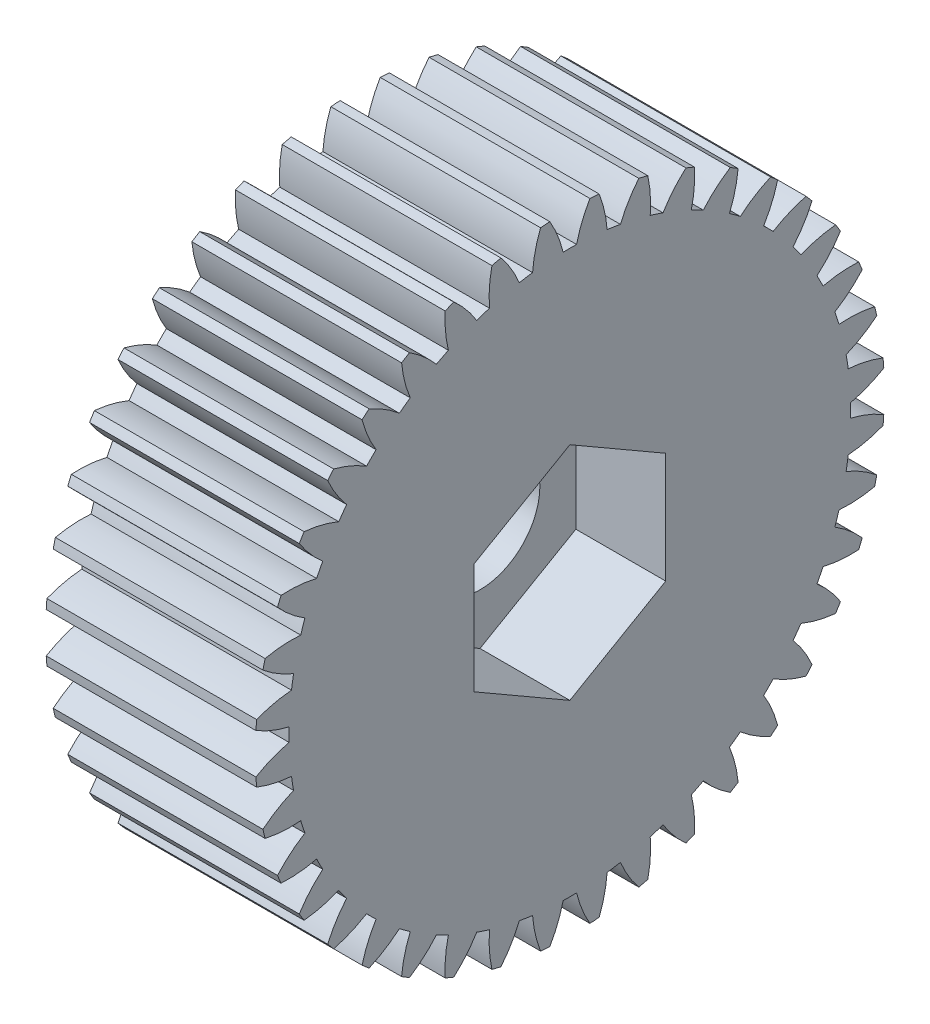
SolidWorks part; units mm, degrees
ref_plane "Plane1" through (0, 0, 0) normal (0, 0, 1) x (1, 0, 0)
ref_plane "Plane2" through (0, 0, 0) normal (0, 1, 0) x (1, 0, 0)
ref_plane "Plane3" through (0, 0, 0) normal (1, 0, 0) x (0, 0, -1)
sketch "HoldingSke" plane through (0, 0, 0) normal (0, 1, 0) x (1, 0, 0)
  line L0 (0, 0) -> (0.766, -0.6428)
  line L1 (-15, 0) -> (100, 0) construction
  line L2 (0, 0) -> (-2.1039, 2.3779)
  line L3 (0, 0) -> (-11.863, 4.5341)
  line L4 (0, 0) -> (6.6156, 5.5511)
  line L5 (0, 0) -> (-46.8476, -17.4728)
  line L6 (0, 0) -> (-11.6055, -7.8303)
  line L7 (-2.1039, 2.3779) -> (8.6586, 51.2059)
  line L8 (-76.2, 54.61) -> (-75.5, 54.61)
  line L9 (-71.009, 38.7566) -> (-53.1078, 45.2721)
  line L10 (-76.2, 71.12) -> (104.1128, 71.12)
  line L11 (0, 0) -> (-14, 0)
  line L12 (-76.2, 101.6) -> (-76.162, 101.6)
  line L13 (24.9733, 27.94) -> (52.9518, 28.4284)
  line L14 (24.9733, 27.94) -> (24.9743, 27.94)
  line L15 (24.9733, 27.94) -> (100.4006, 29.5858)
  line L16 (-63.627, -1) -> (-12.827, -1)
  circle A0 centre (0, 0) radius 2
  circle A1 centre (0, 0) radius 18.749
  circle A2 centre (0, 0) radius 37.5
  circle A3 centre (0, 0) radius 2
  dimension "MHD" = 37.498
  dimension "Hub_dia" = 75
  dimension "Bore" = 4
  dimension "MBD" = 4
  dimension "Num_teeth" = 40
  dimension "Pitch" = 1
  dimension "Overall_len" = 50
  dimension "Show_teeth" = 40
  dimension "Thickness" = 14
  dimension "OAL" = 50.0001
  dimension "T_dim" = 0.7
  dimension "Ap" = 20
  dimension "H" = 19.05
  dimension "Pitch_radius" = 180.3128
  dimension "Width" = 14
  dimension "Backlash" = 0.038
  dimension "Addendum_fac" = 1
  dimension "Dedendum_fac" = 1.25
  dimension "Clearance_fac" = 0.25
  dimension "Dedendum_add" = 0.001
  dimension "Module" = 1
sketch "BasProSke" plane through (0, 0, 0) normal (0, 1, 0) x (1, 0, 0)
  line L0 (-10, 0) -> (60, 0) construction
  line L1 (0, 0) -> (0, 21)
  line L2 (0, 0) -> (14, 0)
  line L3 (14, 0) -> (14, 21)
  line L4 (14, 21) -> (0, 21)
  dimension "Thickness" = 14
  dimension "Diameter" = 42
revolve "Base-Revolve" add sketch "BasProSke" angle 360 about L0
sketch "TooCutSke" plane through (0, 0, 0) normal (1, 0, 0) x (0, 0, -1)
  line L1 (0, 0) -> (0, 107) construction
  line L2 (0, 0) -> (-0.8517, 19.9819) construction
  line L3 (0, 0) -> (-3.1363, 39.8509) construction
  line L4 (-0.8517, 19.9819) -> (-1.5682, 19.9255) construction
  arc A0 (0.4487, 18.7436) -> (-0.4487, 18.7436) centre (0, 0) ccw
  arc A1 (1.3547, 20.9817) -> (-1.3547, 20.9817) centre (0, 0) ccw
  circle A2 centre (0, 0) radius 20 construction
  circle A3 centre (0, 0) radius 18.7939 construction
  arc A4 (-0.4487, 18.7436) -> (-1.3547, 20.9817) centre (-8.2322, 16.895) ccw
  arc A5 (1.3547, 20.9817) -> (0.4487, 18.7436) centre (8.2322, 16.895) ccw
  dimension "Root_dia" = 37.498
  dimension "Overcut_dia" = 42.0508
  dimension "Pitch_dia" = 40
  dimension "Base_dia" = 37.5877
  dimension "Flank_rad" = 8
  dimension "Half_ang" = 4.5
  dimension "Half_CT" = 0.7187
extrude "ToothCut" cut sketch "TooCutSke" along normal through all
fillet "Breaks" [suppressed] radius 0.02 tangent propagation no
fillet "RootFillets" [suppressed] radius 0.251
pattern_circular "TeethCuts" count 40 every 9 about axis through (-10, 0, 0) along (1, 0, 0) of "ToothCut", "RootFillets", "Breaks"
sketch "HubNeaOneSke" plane through (0, 0, 0) normal (-1, 0, 0) x (0, 0, 1)
  circle A0 centre (0, 0) radius 18.749
  dimension "Diameter" = 37.498
extrude "HubNearOne" [suppressed] add sketch "HubNeaOneSke" along normal blind 36.0001
sketch "HubNeaBotSke" plane through (0, 0, 0) normal (-1, 0, 0) x (0, 0, 1)
  circle A0 centre (0, 0) radius 18.749
  dimension "Diameter" = 37.498
extrude "HubNearBoth" [suppressed] add sketch "HubNeaBotSke" along normal blind 18
ref_plane "FarPln" through (14, 0, 0) normal (1, 0, 0) x (0, 0, -1)
sketch "HubFarSke" plane through (14, 0, 0) normal (1, 0, 0) x (0, 0, -1)
  circle A0 centre (0, 0) radius 18.749
  dimension "Diameter" = 37.498
extrude "HubFar" [suppressed] add sketch "HubFarSke" along normal blind 18
sketch "BorSke" plane through (0, 0, 0) normal (1, 0, 0) x (0, 0, -1)
  circle A0 centre (0, 0) radius 2
extrude "Bore" cut sketch "BorSke" along normal mid plane 100.0001
sketch "KeySke" plane through (0, 0, 0) normal (1, 0, 0) x (0, 0, -1)
  line L0 (-0.8, 0) -> (-0.8, 2.7)
  line L1 (-0.8, 2.7) -> (0.8, 2.7)
  line L2 (0.8, 2.7) -> (0.8, 0)
  line L3 (0, 0) -> (0, 34) construction
  line L4 (-0.8, 0) -> (0.8, 0)
  dimension "Offset" = 2.7
  dimension "Width" = 1.6
extrude "Keyway" [suppressed] cut sketch "KeySke" along normal mid plane 100.0001
pattern_circular "Keyway2" [suppressed] count 2 every 90 about axis through (-10, 0, 0) along (1, 0, 0)
sketch "Sketch1" plane through (14, 0, 0) normal (1, 0, 0) x (0, 0, -1)
  line L1 (0, 7.3901) -> (-6.4, 3.695)
  line L2 (-6.4, 3.695) -> (-6.4, -3.695)
  line L3 (-6.4, -3.695) -> (0, -7.3901)
  line L4 (0, -7.3901) -> (6.4, -3.695)
  line L5 (6.4, -3.695) -> (6.4, 3.695)
  line L6 (6.4, 3.695) -> (0, 7.3901)
  circle A0 centre (0, 0) radius 7.3901
  circle A2 centre (0, 0) radius 6.4 construction
  circle A3 centre (0, 0) radius 4
  dimension "D1" = 8
  dimension "D2" = 12.8
extrude "Cut-Extrude1" cut sketch "Sketch1" against normal blind 6 contours L1 L2 L3 L4 L5 L6
extrude "Cut-Extrude2" cut sketch "Sketch1<7>" against normal through all contours A3 region at (14, 0, 0)
sketch "Sketch1<7>" plane through (14, 0, 0) normal (1, 0, 0) x (0, 0, -1) same geometry as "Sketch1"
sketch "Sketch2" plane through (0, 0, 0) normal (-1, 0, 0) x (0, 0, 1)
  circle A0 centre (0, 0) radius 6.5
  circle A1 centre (0, 0) radius 4
  dimension "D1" = 13
  dimension "D2" = 8
extrude "Boss-Extrude1" add sketch "Sketch2" along normal blind 3.8
sketch "Sketch3" plane through (8, 0, 0) normal (1, 0, 0) x (0, 0, -1)
  line L1 (4, 4) -> (-4, 4)
  line L2 (4, 4) -> (4, -4)
  line L3 (4, -4) -> (-4, -4)
  line L4 (-4, 4) -> (-4, -4)
  line L6 (5.5, 5.5) -> (5.5, -5.5)
  line L7 (5.5, -5.5) -> (-5.5, -5.5)
  line L8 (-5.5, 5.5) -> (-5.5, -5.5)
  line L9 (5.5, 5.5) -> (-5.5, 5.5)
  line L10 (5.5, 4) -> (5.8718, 4)
  line L11 (6.4, 3.695) -> (0, 7.3901) construction
  line L12 (5.5, -4) -> (5.8718, -4)
  line L13 (0, -7.3901) -> (6.4, -3.695) construction
  line L14 (-5.5, -4) -> (-5.8718, -4)
  line L15 (-6.4, -3.695) -> (0, -7.3901) construction
  line L16 (-5.5, 4) -> (-5.8718, 4)
  line L17 (0, 7.3901) -> (-6.4, 3.695) construction
  circle A0 centre (0, 0) radius 4 construction
  line M10 (6.4, 3.695) -> (0, 7.3901)
  line M11 (0, 7.3901) -> (-6.4, 3.695)
  line M13 (-6.4, -3.695) -> (0, -7.3901)
  line M14 (0, -7.3901) -> (6.4, -3.695)
  dimension "D1" = 1.5
extrude "Boss-Extrude2" [suppressed] add sketch "Sketch3" along normal blind 0.3 contours L9 L8 L7 L6 L4 L1 L2 L3 M10 M11 M13 M14 | L12 L6 M14 | L6 L10 M10 | L16 L8 M11 | L8 L14 M13
equation "' \"Module@HoldingSke\" = 6.35"
equation "' \"Num_teeth@HoldingSke\" = 12"
equation "' \"Ap@HoldingSke\" =  20"
equation "' \"Ap@HoldingSke\" = 20"
equation "' \"Width@HoldingSke\" = 0.5 * 25.4"
equation "' \"Hub_dia@HoldingSke\"= 1 * 25.4"
equation "' \"Hub_dia@HoldingSke\" = 1 * 25.4"
equation "' \"Overall_len@HoldingSke\" = 1.0 * 25.4"
equation "' \"Bore@HoldingSke\" = 0.75 * 25.4"
equation "' \"T_dim@HoldingSke\" = 0.1 * 25.4"
equation "' \"Width@KeySke\" = 0.25 * 25.4"
equation "' \"Show_teeth@HoldingSke\" = 13"
equation "' \"Backlash@HoldingSke\" = 0.009 * 25.4"
equation "' \"Addendum_fac@HoldingSke\" = 1.0"
equation "' \"Dedendum_fac@HoldingSke\" = 1.25"
equation "' \"Dedendum_add@HoldingSke\" = 0.00005 * 25.4"
equation "' \"Clearance_fac@HoldingSke\" = 0.25"
equation "\"Pitch@HoldingSke\" = 1 / \"Module@HoldingSke\""
equation "\"Overcut_dia@TooCutSke\" = (\"Num_teeth@HoldingSke\" + 2 * \"Addendum_fac@HoldingSke\") / \"Pitch@HoldingSke\" + 0.002 * 25.4"
equation "\"Pitch_dia@TooCutSke\" = \"Num_teeth@HoldingSke\" / \"Pitch@HoldingSke\""
equation "\"Base_dia@TooCutSke\" = \"Num_teeth@HoldingSke\" / \"Pitch@HoldingSke\" * cos((\"Ap@HoldingSke\"  * 3.14159265 / 180))"
equation "\"Root_dia@TooCutSke\" = (\"Num_teeth@HoldingSke\" + 2) / \"Pitch@HoldingSke\" - 2 * (\"Addendum_fac@HoldingSke\" + \"Dedendum_fac@HoldingSke\") / \"Pitch@HoldingSke\" - \"Dedendum_add@HoldingSke\" * 2"
equation "\"Half_ang@TooCutSke\" = 180 / \"Num_teeth@HoldingSke\""
equation "\"Half_CT@TooCutSke\" = \"Num_teeth@HoldingSke\" / \"Pitch@HoldingSke\" * sin((3.14159265 / 2 / \"Num_teeth@HoldingSke\")) / 2 - 7 * \"Backlash@HoldingSke\" / 4"
equation "\"Flank_rad@TooCutSke\" = \"Num_teeth@HoldingSke\" / \"Pitch@HoldingSke\" / 5"
equation "\"Radius@RootFillets\" = \"Clearance_fac@HoldingSke\" / \"Pitch@HoldingSke\" + \"Dedendum_add@HoldingSke\""
equation "\"Break_rad@Breaks\" = 0.02 / \"Pitch@HoldingSke\""
equation "\"Thickness@HoldingSke\" = \"Width@HoldingSke\""
equation "\"OAL@HoldingSke\" = \"Thickness@HoldingSke\""
equation "\"MHD@HoldingSke\" = (\"Num_teeth@HoldingSke\" + 2) / \"Pitch@HoldingSke\" - 2 * (\"Addendum_fac@HoldingSke\" + \"Dedendum_fac@HoldingSke\")  / \"Pitch@HoldingSke\" - \"Dedendum_add@HoldingSke\" * 2"
equation "\"MBD@HoldingSke\" = (\"Num_teeth@HoldingSke\" + 2) / \"Pitch@HoldingSke\" - 2 * (\"Addendum_fac@HoldingSke\" + \"Dedendum_fac@HoldingSke\")  / \"Pitch@HoldingSke\" - \"Dedendum_add@HoldingSke\" * 2 - 0.002 * 25.4"
equation "\"MHD@HoldingSke\" = ((sgn( \"MHD@HoldingSke\" - \"Hub_dia@HoldingSke\" )-1)*( \"MHD@HoldingSke\" - \"Hub_dia@HoldingSke\" ))/-2+ \"Hub_dia@HoldingSke\""
equation "\"MBD@HoldingSke\" = ((sgn( \"MBD@HoldingSke\" - \"Bore@HoldingSke\" )-1)*( \"MBD@HoldingSke\" - \"Bore@HoldingSke\" ))/-2+ \"Bore@HoldingSke\""
equation "\"OAL@HoldingSke\" = ((sgn( \"OAL@HoldingSke\" - \"Overall_len@HoldingSke\" )+1)*( \"OAL@HoldingSke\" - \"Overall_len@HoldingSke\" ))/2 + \"Overall_len@HoldingSke\" + 0.000002 * 25.4"
equation "\"Num_teeth@TeethCuts\" = int( \"Show_teeth@HoldingSke\" ) + 1"
equation "\"Num_teeth@TeethCuts\" = ((sgn( \"Num_teeth@TeethCuts\" - \"Num_teeth@HoldingSke\" )-1)*( \"Num_teeth@TeethCuts\" - \"Num_teeth@HoldingSke\" ))/-2+ \"Num_teeth@HoldingSke\""
equation "\"Num_teeth@TeethCuts\" = ((sgn( \"Num_teeth@TeethCuts\" - 2.0)+1)*( \"Num_teeth@TeethCuts\" - 2.0))/2 +2.0"
equation "\"Angle@TeethCuts\" = 360.0 / \"Num_teeth@HoldingSke\""
equation "\"Diameter@BasProSke\" = (\"Num_teeth@HoldingSke\" + 2 * \"Addendum_fac@HoldingSke\") / \"Pitch@HoldingSke\""
equation "\"Thickness@BasProSke\"  = \"Thickness@HoldingSke\""
equation "' \"Fillet_rad@BasProSke\" =  \"Thickness@HoldingSke\" * 0.05"
equation "' \"Fillet_rad@BasProSke\" = \"Thickness@HoldingSke\" * 0.05"
equation "\"MHD@HoldingSke\" = ((sgn( \"MHD@HoldingSke\" - \"Root_dia@TooCutSke\" )-1)*( \"MHD@HoldingSke\" - \"Root_dia@TooCutSke\" ))/-2+ \"Root_dia@TooCutSke\""
equation "\"Diameter@HubNeaOneSke\" = \"MHD@HoldingSke\""
equation "\"Length@HubNearOne\" = \"OAL@HoldingSke\" - \"Thickness@BasProSke\""
equation "\"Diameter@HubNeaBotSke\" = \"MHD@HoldingSke\""
equation "\"Length@HubNearBoth\" = ( \"OAL@HoldingSke\" - \"Thickness@BasProSke\" ) / 2.0"
equation "\"Thickness@FarPln\" = \"Thickness@BasProSke\""
equation "\"Diameter@HubFarSke\" = \"MHD@HoldingSke\""
equation "\"Length@HubFar\" = ( \"OAL@HoldingSke\" - \"Thickness@BasProSke\" ) / 2.0"
equation "\"Diameter@BorSke\" = \"MBD@HoldingSke\""
equation "\"D1@Bore\" = \"OAL@HoldingSke\" * 2.0"
equation "\"D1@Keyway\" = \"OAL@HoldingSke\" * 2.0"
equation "\"Offset@KeySke\" = \"T_dim@HoldingSke\" + \"MBD@HoldingSke\" / 2.0"
